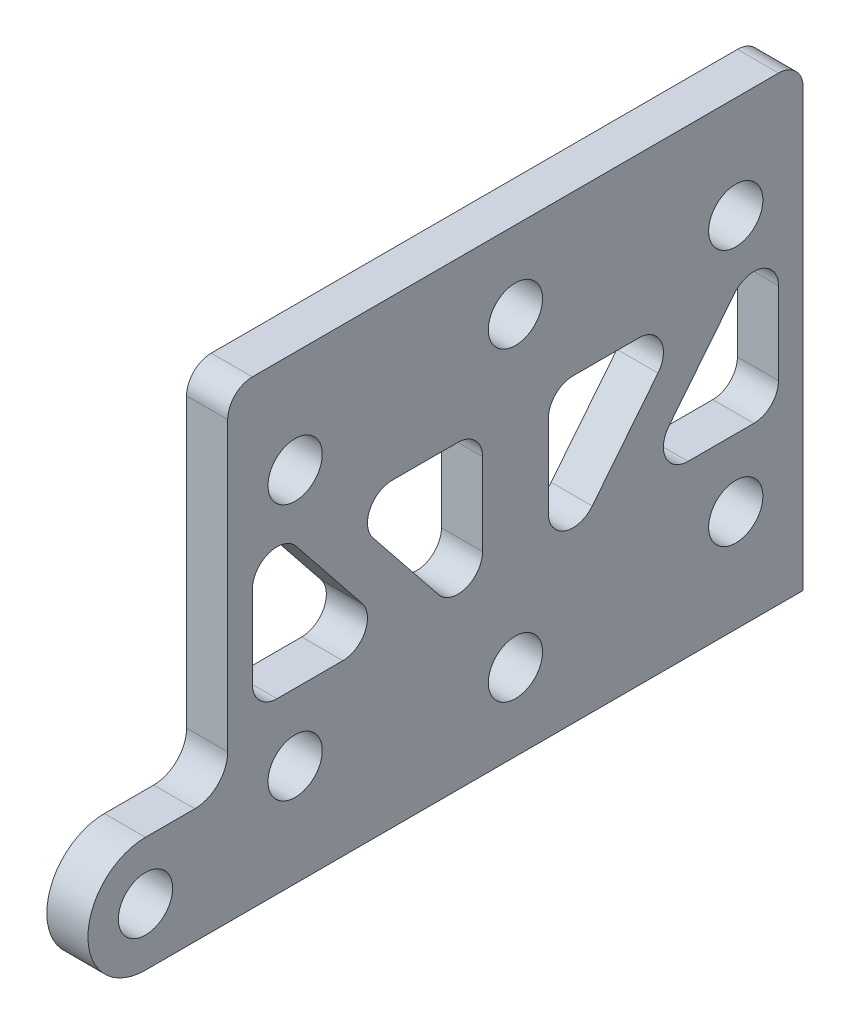
SolidWorks part; units mm, degrees
ref_plane "Ön Düzlem" through (0, 0, 0) normal (0, 0, 1) x (1, 0, 0)
ref_plane "Üst Düzlem" through (0, 0, 0) normal (0, 1, 0) x (1, 0, 0)
ref_plane "Sağ Düzlem" through (0, 0, 0) normal (1, 0, 0) x (0, 0, -1)
sketch "Çizim1" plane through (0, 0, 0) normal (1, 0, 0) x (0, 0, -1)
  line L0 (-17.5, 0) -> (-17.5, 28) construction
  line L1 (0, 0) -> (-35, 0)
  line L2 (0, 0) -> (0, 26.5)
  line L3 (-1.5, 28) -> (-33.5, 28)
  line L4 (-35, 0) -> (-35, 8.2)
  line L5 (-35, 8.2) -> (-35, 28)
  line L6 (-35, 28) -> (-33.5, 28)
  line L7 (-35, 7) -> (-43.5, 7)
  line L8 (-43.5, 7) -> (-43.5, 0)
  line L9 (-43.5, 0) -> (-35, 0)
  line L10 (-35, 14) -> (0, 14) construction
  arc A0 (0, 26.5) -> (-1.5, 28) centre (-1.5, 26.5) ccw
  circle A2 centre (-30.9, 6.2) radius 1.65
  circle A3 centre (-4.1, 6.2) radius 1.65
  circle A4 centre (-17.5, 4.7) radius 1.65
  circle A5 centre (-40, 3.5) radius 1.65
  circle A6 centre (-4.1, 21.8) radius 1.65
  circle A7 centre (-17.5, 23.3) radius 1.65
  circle A8 centre (-30.9, 21.8) radius 1.65
  point P7 (0, 28)
  point P10 (-35, 28)
  point P25 (-43.5, 3.5)
  dimension "D3" = 1.5
  dimension "D4" = 3.3
  dimension "D9" = 3.3
  dimension "D1" = 28
  dimension "D2" = 35
  dimension "D5" = 6.2
  dimension "D6" = 4.1
  dimension "D7" = 4.1
  dimension "D8" = 4.7
  dimension "D10" = 7
  dimension "D11" = 8.5
  dimension "D12" = 5
  dimension "D13" = 14
extrude "Yükseklik-Ekstrüzyon1" add sketch "Çizim1" along normal blind 2.5 contours L0 L1 L2 A0 L3 A4 A3 | L1 L0 A4 L3 L6 L5 L4 A2 | L8 L9 L4 L7 A5 region at (0, 13.9929, 17.5089) region at (0, 0.1101, 39.25)
fillet "Radyus1" 2 edges at (1.25, 7, 43.5) (1.25, 0, 43.5) type full round first side face at (1.25, 7, 39.25) second side face at (1.25, 0, 21.75) middle face at (1.25, 3.5, 43.5)
fillet "Radyus3" radius 2 1 edges at (1.25, 7, 35)
fillet "Radyus4" radius 1.5 1 edges at (1.25, 28, 35)
sketch "Çizim2" plane through (2.5, 0, 0) normal (1, 0, 0) x (0, 0, -1)
  line L0 (-17.5, 28) -> (-17.5, 0) construction
  line L1 (-1.5, 28) -> (-33.5, 28) construction
  line L2 (0, 0) -> (-40, 0) construction
  line L3 (-33.5, 16.8) -> (-33.5, 11.8)
  line L4 (-32, 10.3) -> (-28, 10.3)
  line L5 (-26.8287, 12.737) -> (-30.8287, 17.737)
  line L6 (-25, 18.3) -> (-21, 18.3)
  line L7 (-19.5, 16.8) -> (-19.5, 11.8)
  line L8 (-22.1713, 10.863) -> (-26.1713, 15.863)
  line L9 (-35, 9) -> (-35, 26.5) construction
  line L10 (-12.8287, 10.863) -> (-8.8287, 15.863)
  line L11 (-15.5, 16.8) -> (-15.5, 11.8)
  line L12 (-10, 18.3) -> (-14, 18.3)
  line L13 (-8.1713, 12.737) -> (-4.1713, 17.737)
  line L14 (-3, 10.3) -> (-7, 10.3)
  line L15 (-1.5, 16.8) -> (-1.5, 11.8)
  arc A0 (-19.5, 11.8) -> (-22.1713, 10.863) centre (-21, 11.8) cw
  arc A1 (-21, 18.3) -> (-19.5, 16.8) centre (-21, 16.8) cw
  arc A2 (-25, 18.3) -> (-26.1713, 15.863) centre (-25, 16.8) ccw
  arc A3 (-28, 10.3) -> (-26.8287, 12.737) centre (-28, 11.8) ccw
  arc A4 (-33.5, 11.8) -> (-32, 10.3) centre (-32, 11.8) ccw
  arc A5 (-33.5, 16.8) -> (-30.8287, 17.737) centre (-32, 16.8) cw
  circle A6 centre (-30.9, 21.8) radius 1.65 construction
  arc A7 (-1.5, 16.8) -> (-4.1713, 17.737) centre (-3, 16.8) ccw
  arc A8 (-1.5, 11.8) -> (-3, 10.3) centre (-3, 11.8) cw
  arc A9 (-7, 10.3) -> (-8.1713, 12.737) centre (-7, 11.8) cw
  arc A10 (-10, 18.3) -> (-8.8287, 15.863) centre (-10, 16.8) cw
  arc A11 (-14, 18.3) -> (-15.5, 16.8) centre (-14, 16.8) ccw
  arc A12 (-15.5, 11.8) -> (-12.8287, 10.863) centre (-14, 11.8) ccw
  dimension "D1" = 1.5
  dimension "D2" = 4
  dimension "D3" = 5
  dimension "D4" = 5
  dimension "D5" = 3
  dimension "D6" = 7
extrude "Kes-Ekstrüzyon1" cut sketch "Çizim2" against normal through all
